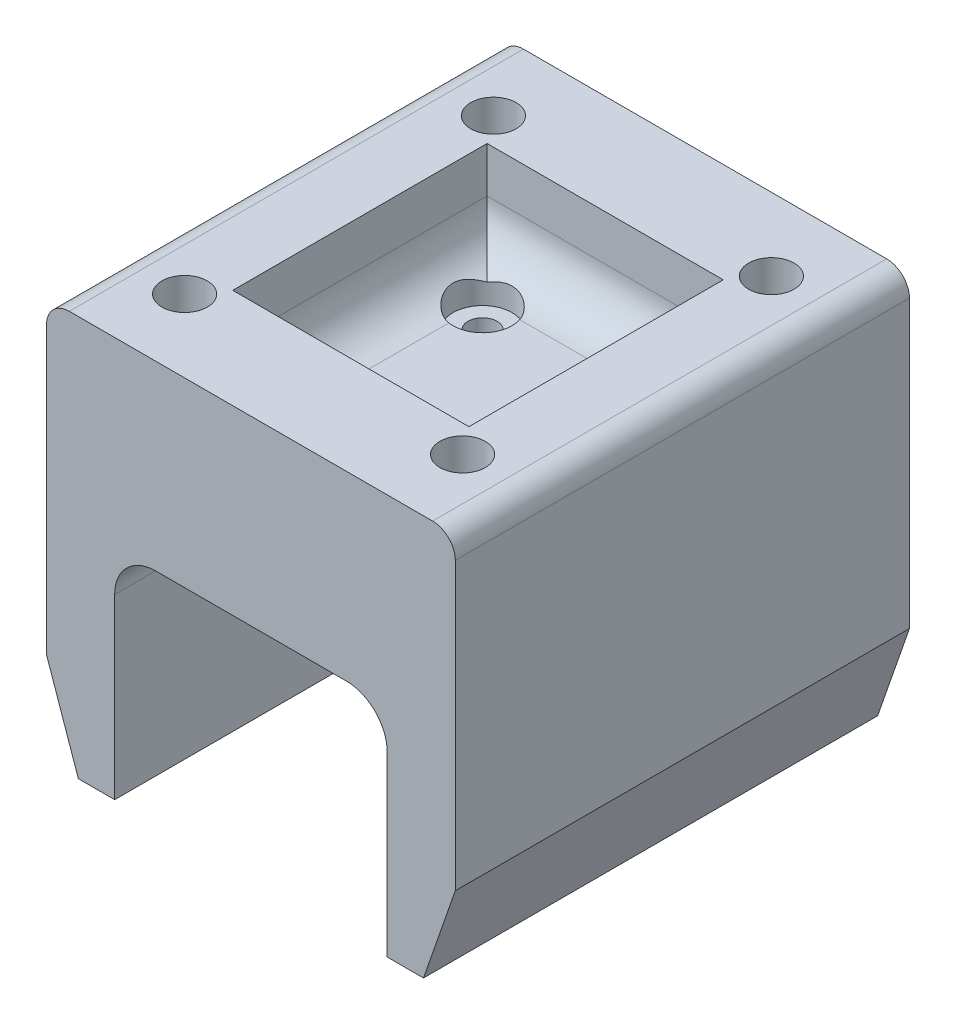
SolidWorks part; units mm, degrees
material "ABS"
ref_plane "Alzado" through (0, 0, 0) normal (0, 0, 1) x (1, 0, 0)
ref_plane "Planta" through (0, 0, 0) normal (0, 1, 0) x (1, 0, 0)
ref_plane "Vista lateral" through (0, 0, 0) normal (1, 0, 0) x (0, 0, -1)
sketch "Sketch1" plane through (0, 0, 0) normal (0, 1, 0) x (1, 0, 0)
  line L1 (-22.5, -25) -> (22.5, -25)
  line L2 (-22.5, -25) -> (-22.5, 25)
  line L3 (-22.5, 25) -> (22.5, 25)
  line L4 (22.5, -25) -> (22.5, 25)
  line L5 (-22.5, -25) -> (22.5, 25) construction
  line L6 (-22.5, 25) -> (22.5, -25) construction
  line L7 (-7.5, -8) -> (7.5, -8) construction
  line L8 (-7.5, -8) -> (-7.5, 8) construction
  line L9 (-7.5, 8) -> (7.5, 8) construction
  line L10 (7.5, -8) -> (7.5, 8) construction
  line L11 (-7.5, -8) -> (7.5, 8) construction
  line L12 (-7.5, 8) -> (7.5, -8) construction
  circle A0 centre (-7.5, 8) radius 1.5
  circle A1 centre (7.5, 8) radius 1.5
  circle A2 centre (7.5, -8) radius 1.5
  circle A3 centre (-7.5, -8) radius 1.5
  circle A4 centre (15.3, 17) radius 2.5
  circle A5 centre (-15.3, 17) radius 2.5
  circle A6 centre (-15.3, -17) radius 2.5
  circle A7 centre (15.3, -17) radius 2.5
  point P0 (0, 0)
  point P6 (0, 0)
  dimension "D5" = 3
  dimension "D7" = 5
  dimension "D1" = 45
  dimension "D2" = 50
  dimension "D3" = 16
  dimension "D4" = 15
  dimension "D6" = 34
  dimension "D8" = 17
extrude "Boss-Extrude1" add sketch "Sketch1" along normal blind 20
sketch "Sketch3" plane through (0, 20, 0) normal (0, 1, 0) x (1, 0, 0)
  line L1 (-13, -14) -> (13, -14)
  line L2 (-13, -14) -> (-13, 14)
  line L3 (-13, 14) -> (13, 14)
  line L4 (13, -14) -> (13, 14)
  line L5 (-13, -14) -> (13, 14) construction
  line L6 (-13, 14) -> (13, -14) construction
  point P0 (0, 0)
  dimension "D1" = 28
  dimension "D2" = 26
extrude "Cut-Extrude1" cut sketch "Sketch3" against normal blind 10
sketch "Sketch7" plane through (0, 10, 0) normal (0, 1, 0) x (1, 0, 0)
  point P0 (-7.5, 8)
  point P3 (-7.5, -8)
  point P6 (7.5, -8)
  point P9 (7.5, 8)
hole_wizard "Refrentado para tornillo con cabeza plana de M32" positions "Sketch7" profile "Sketch8" counterbore size "M3" standard "ISO" end condition through all
sketch "Sketch8" plane through (-7.5, 10, -8) normal (1, 0, 0) x (0, 0, 1)
  line L0 (0, 0) -> (0, 10)
  line L1 (0, 10) -> (1.6, 10)
  line L3 (1.6, 10) -> (1.6, 2)
  line L4 (1.6, 2) -> (3.25, 2)
  line L5 (3.25, 2) -> (3.25, 0)
  line L7 (3.25, 0) -> (0, 0)
  line L11 (0, -6.35) -> (0, 107.95) construction
  dimension "Diámetro de taladro hasta el siguiente" = 3.2
  dimension "Profundidad de taladro hasta el siguiente" = 10
  dimension "Diámetro de refrentado" = 6.5
  dimension "Profundidad de refrentado" = 2
fillet "Fillet4" radius 5 4 edges at (0, 10, 14) (13, 10, 0) (0, 10, -14) (-13, 10, 0)
sketch "Sketch10" plane through (0, 0, -25) normal (0, 0, -1) x (-1, 0, 0)
  line L15 (-15, 0) -> (-15, -24.0677)
  line L16 (-22.5, 0) -> (22.5, 0) construction
  line L17 (-15, -24.0677) -> (-19, -24.0677)
  line L19 (-19, -24.0677) -> (-22.5, -14)
  line L21 (-22.5, -14) -> (-22.5, 0)
  line L22 (-22.5, 0) -> (-15, 0)
  dimension "D1" = 15
  dimension "D2" = 14
  dimension "D3" = 4
extrude "Boss-Extrude4" add sketch "Sketch10" against normal through all
mirror "Mirror1" about plane through (0, 0, 0) normal (1, 0, 0) of "Boss-Extrude4"
fillet "Fillet5" radius 4.5 2 edges at (15, 0, 0) (-15, 0, 0)
fillet "Fillet6" radius 2.5 2 edges at (22.5, 20, 0) (-22.5, 20, 0)
